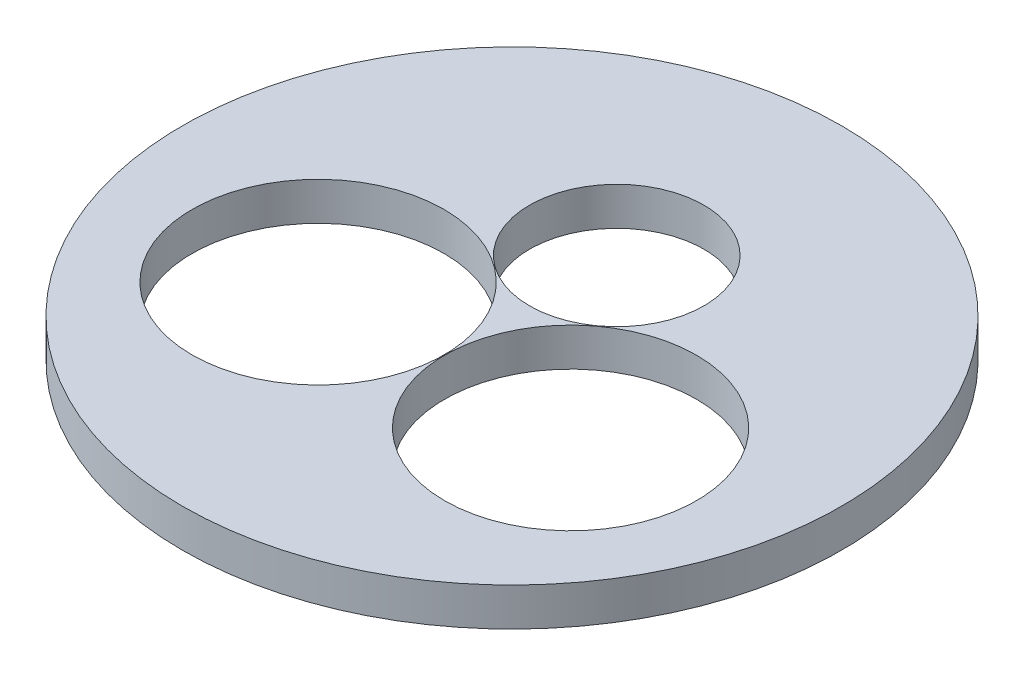
SolidWorks part; units mm, degrees
ref_plane "Front Plane" through (0, 0, 0) normal (0, 0, 1) x (1, 0, 0)
ref_plane "Top Plane" through (0, 0, 0) normal (0, 1, 0) x (1, 0, 0)
ref_plane "Right Plane" through (0, 0, 0) normal (1, 0, 0) x (0, 0, -1)
sketch "Sketch1" plane through (0, 0, 0) normal (0, 1, 0) x (1, 0, 0)
  line L0 (-330.835, -177.3911) -> (0, 0) construction
  line L1 (-330.835, -177.3911) -> (330.835, -177.3911) construction
  line L2 (330.835, -177.3911) -> (0, 274.5232) construction
  line L3 (0, 274.5232) -> (-330.835, -177.3911) construction
  line L4 (0, 0) -> (330.835, -177.3911) construction
  circle A2 centre (330.835, -177.3911) radius 330.2
  circle A5 centre (0, 0) radius 863.6
  circle A6 centre (0, 274.5232) radius 228.6
  circle A8 centre (-330.835, -177.3911) radius 330.2
  dimension "D1" = 1727.2
  dimension "D2" = 177.3911
  dimension "D3" = 660.4
  dimension "D4" = 660.4
  dimension "D5" = 457.2
  dimension "D7" = 661.67
  dimension "D8" = 560.07
  dimension "D9" = 560.07
extrude "Boss-Extrude1" add sketch "Sketch1" along normal blind 100
